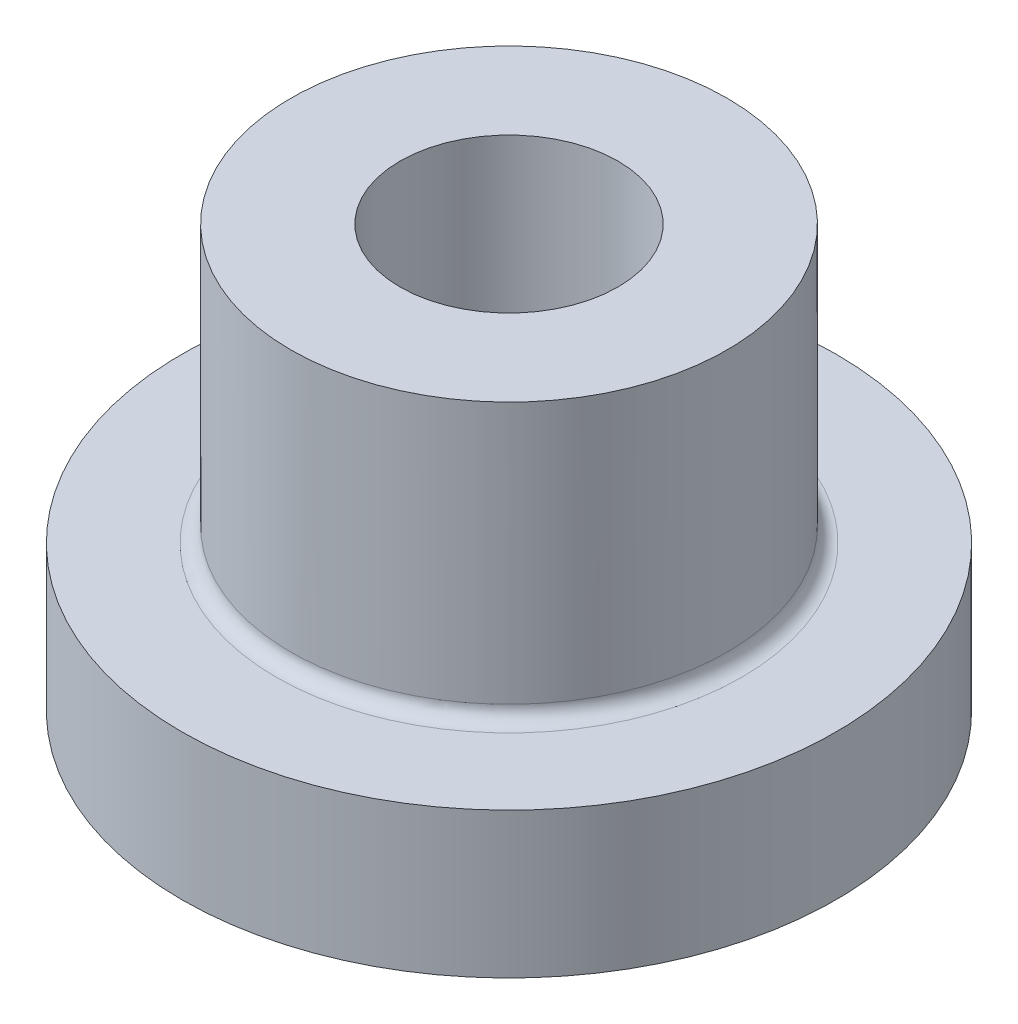
SolidWorks part; units mm, degrees
ref_plane "Front Plane" through (0, 0, 0) normal (0, 0, 1) x (1, 0, 0)
ref_plane "Top Plane" through (0, 0, 0) normal (0, 1, 0) x (1, 0, 0)
ref_plane "Right Plane" through (0, 0, 0) normal (1, 0, 0) x (0, 0, -1)
sketch "Sketch1" plane through (0, 0, 0) normal (0, 1, 0) x (1, 0, 0)
  circle A0 centre (0, 0) radius 3
  dimension "D1" = 6
extrude "Boss-Extrude1" add sketch "Sketch1" along normal blind 4.2
shell "Shell1" thickness 1.5 removed face at (0, 0, 3) removed face at (0, 4.2, 3)
sketch "Sketch2" plane through (0, 0, 0) normal (0, -1, 0) x (1, 0, 0)
  circle A0 centre (0, 0) radius 3 construction
  circle A1 centre (0, 0) radius 3
  circle A2 centre (0, 0) radius 4.5
  dimension "D1" = 1.5
extrude "Boss-Extrude2" add sketch "Sketch2" along normal blind 1.6 and the other way blind 0.4
fillet "Fillet4" radius 0.2 2 edges at (0, 0, 3) (0, 0.4, -3)
